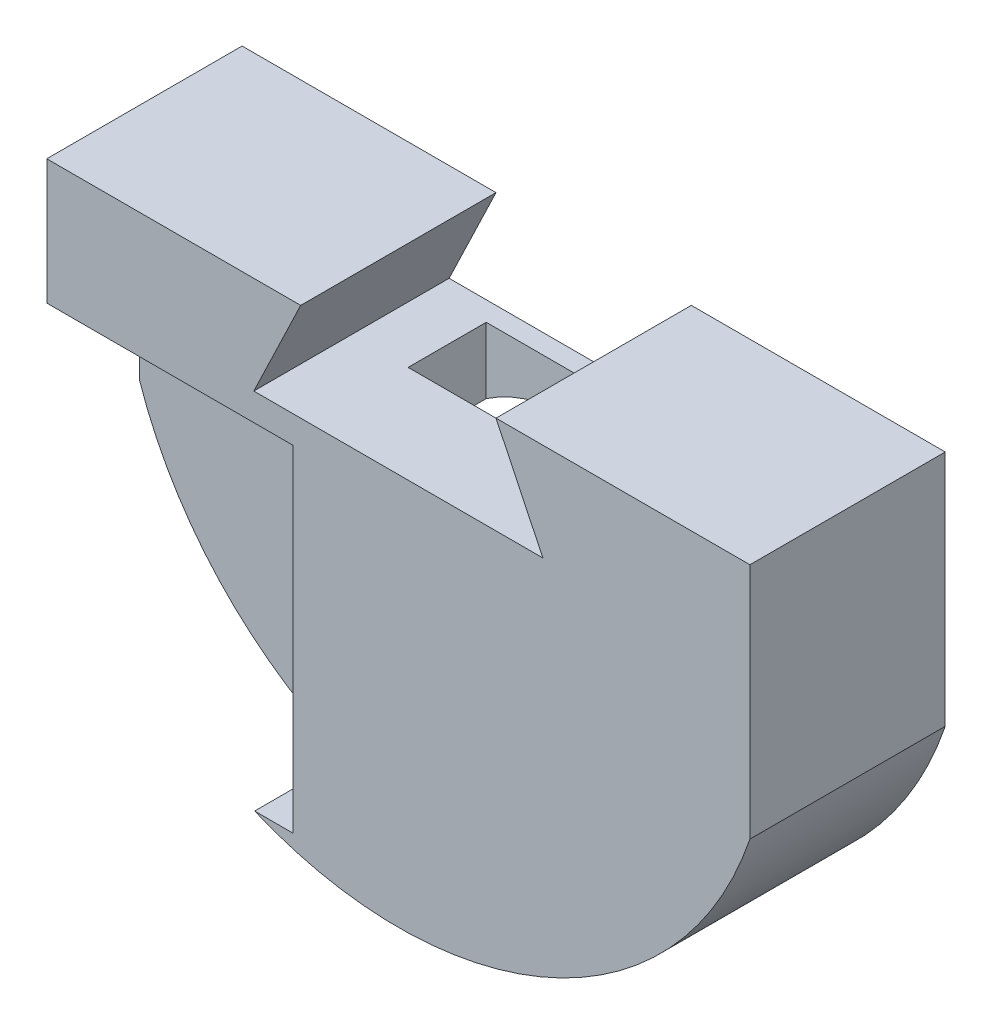
SolidWorks part; units mm, degrees
ref_plane "Front Plane" through (0, 0, 0) normal (0, 0, 1) x (1, 0, 0)
ref_plane "Top Plane" through (0, 0, 0) normal (0, 1, 0) x (1, 0, 0)
ref_plane "Right Plane" through (0, 0, 0) normal (1, 0, 0) x (0, 0, -1)
sketch "Sketch1" plane through (0, 0, 0) normal (0, 0, 1) x (1, 0, 0)
  line L0 (-160.9242, -127.6087) -> (-95.9242, -127.6087)
  line L1 (-95.9242, -127.6087) -> (-107.9242, -152.6087)
  line L2 (-107.9242, -152.6087) -> (-33.9242, -152.6087)
  line L3 (-33.9242, -152.6087) -> (-45.9242, -127.6087)
  line L4 (-45.9242, -127.6087) -> (19.0758, -127.6087)
  line L5 (19.0758, -127.6087) -> (19.0758, -277.6087)
  line L6 (19.0758, -277.6087) -> (-160.9242, -277.6087)
  line L7 (-160.9242, -277.6087) -> (-160.9242, -127.6087)
extrude "Boss-Extrude1" add sketch "Sketch1" along normal blind 50
sketch "Sketch2" plane through (0, 0, 0) normal (0, 0, -1) x (-1, 0, 0)
  line L0 (160.9242, -127.6087) -> (-19.0758, -277.6087) construction
  line L1 (-19.0758, -277.6087) -> (-19.0758, -127.6087) construction
  line L2 (-19.0758, -127.6087) -> (160.9242, -277.6087) construction
  circle A0 centre (70.9242, -202.6087) radius 40
extrude "Cut-Extrude1" cut sketch "Sketch2" against normal blind 30
sketch "Sketch3" plane through (0, -152.6087, 0) normal (0, 1, 0) x (1, 0, 0)
  line L0 (-107.9242, 0) -> (-107.9242, -15) construction
  line L2 (-107.9242, -50) -> (-107.9242, 0) construction
  line L3 (-107.9242, -15) -> (-33.9242, -15) construction
  line L4 (-33.9242, -50) -> (-33.9242, 0) construction
  line L5 (-33.9242, -15) -> (-33.9242, 0) construction
  line L6 (-93.4242, -5) -> (-93.4242, -25)
  line L7 (-93.4242, -25) -> (-48.4242, -25)
  line L8 (-48.4242, -25) -> (-48.4242, -5)
  line L9 (-48.4242, -5) -> (-93.4242, -5)
  point P14 (-93.4242, -15)
  point P16 (-70.9242, -5)
  point P17 (-70.9242, -15)
extrude "Cut-Extrude2" cut sketch "Sketch3" against normal blind 30
sketch "Sketch4" plane through (-160.9242, 0, 0) normal (-1, 0, 0) x (0, 0, 1)
  line L0 (50, -245.6087) -> (26.2925, -245.6087)
  line L1 (50, -127.6087) -> (50, -277.6087) construction
  line L2 (26.2925, -245.6087) -> (26.2925, -159.6087)
  line L3 (26.2925, -159.6087) -> (50, -159.6087)
  line L4 (50, -159.6087) -> (50, -245.6087)
  line L6 (50, -127.6087) -> (0, -127.6087) construction
  line L7 (50, -277.6087) -> (50, -245.6087) construction
  line L8 (50, -159.6087) -> (50, -127.6087) construction
extrude "Cut-Extrude3" cut sketch "Sketch4" against normal blind 53
sketch "Sketch5" plane through (-107.9242, 0, 0) normal (-1, 0, 0) x (0, 0, 1)
  line L0 (26.2925, -245.6087) -> (50, -245.6087) construction
  line L1 (35, -245.6087) -> (50, -245.6087)
  line L2 (35, -245.6087) -> (35, -159.6087)
  line L3 (35, -159.6087) -> (50, -159.6087)
  line L4 (50, -245.6087) -> (50, -159.6087)
extrude "Cut-Extrude4" cut sketch "Sketch5" against normal blind 10
ref_plane "Plane1" through (0, -202.6087, 0) normal (0, -1, 0) x (-1, 0, 0)
sketch "Sketch6" plane through (0, -202.6087, 0) normal (0, -1, 0) x (-1, 0, 0)
  line L0 (36.4455, -13.2221) -> (36.4455, -30.638)
  line L1 (36.4455, -30.638) -> (124.6455, -33.1007)
  line L2 (124.6455, -33.1007) -> (36.4455, -13.2221)
extrude "Cut-Extrude5" cut sketch "Sketch6" against normal blind 10 and the other way blind 10 contours L2 L0 L1
fillet "Fillet6" radius 10 3 edges at (-36.4455, -202.6087, 30) (-72.1849, -212.6087, 30) (-72.1849, -192.6087, 30)
sketch "Sketch7" plane through (0, 0, 0) normal (0, 0, -1) x (-1, 0, 0)
  line L0 (-19.0758, -127.6087) -> (-84.1784, -223.965)
  line L1 (-84.1784, -223.965) -> (33.1596, -359.3118)
  line L2 (33.1596, -359.3118) -> (152.7, -359.3118)
  line L3 (152.7, -359.3118) -> (213.5709, -330.9128)
  line L4 (213.5709, -330.9128) -> (230.8644, -258.9565)
  line L5 (230.8644, -258.9565) -> (230.8644, -247.4397)
  line L6 (160.9242, -127.6087) -> (230.8644, -247.4397)
  arc A0 (-19.0758, -127.6087) -> (160.9242, -127.6087) centre (70.9242, -158.0225) ccw
  point P11 (160.9242, -127.6087)
extrude "Cut-Extrude6" cut sketch "Sketch7" against normal blind 110
